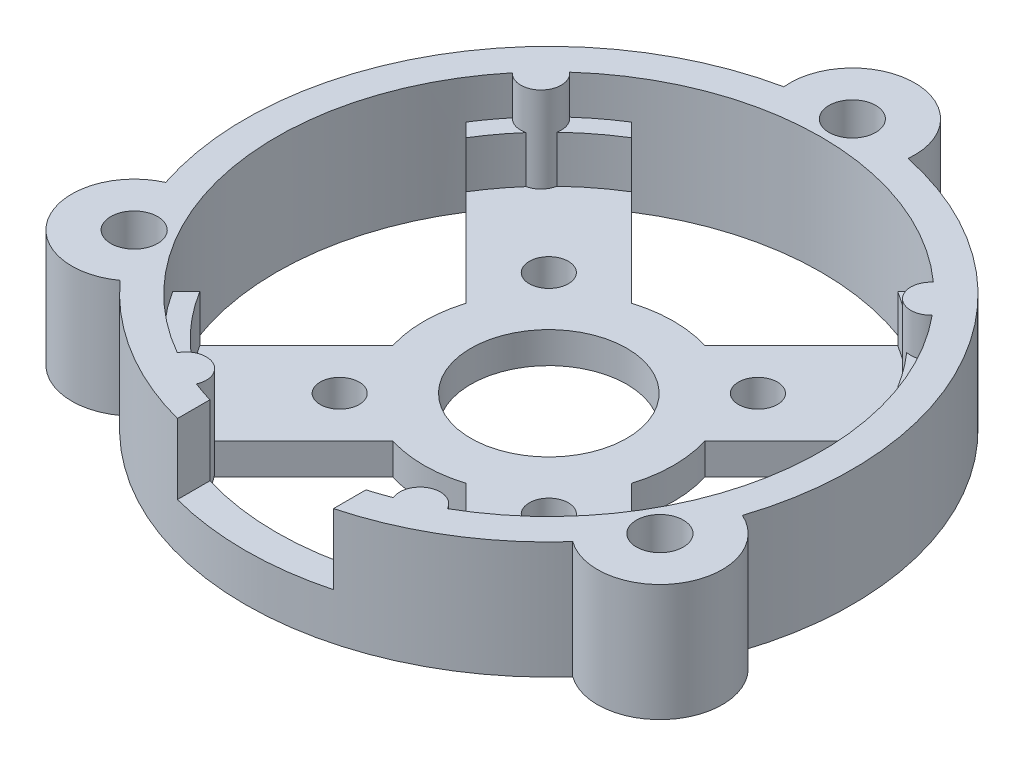
SolidWorks part; units mm, degrees
material "PLA"
ref_plane "Front" through (0, 0, 0) normal (0, 0, 1) x (1, 0, 0)
ref_plane "Top" through (0, 0, 0) normal (0, 1, 0) x (1, 0, 0)
ref_plane "Right" through (0, 0, 0) normal (1, 0, 0) x (0, 0, -1)
other "Configuration Table"
sketch "Esquisse1" plane through (0, 0, 0) normal (0, 1, 0) x (1, 0, 0)
  circle A0 centre (0, 0) radius 17.25 construction
  circle A1 centre (0, 0) radius 17.45
  circle A2 centre (0, 0) radius 19.45
  dimension "D1" = 34.5
  dimension "D2" = 0.2
  dimension "D3" = 2
extrude "Boss.-Extru.1" add sketch "Esquisse1" against normal blind 7.5
sketch "Esquisse2" plane through (0, -7.5, 0) normal (0, -1, 0) x (-1, 0, 0)
  line L0 (-10.8435, -16.1468) -> (16.1468, 10.8435)
  line L1 (-10.8435, -16.1468) -> (-16.1468, -10.8435) construction
  line L2 (16.1468, 10.8435) -> (10.8435, 16.1468) construction
  line L3 (-16.1468, -10.8435) -> (10.8435, 16.1468)
  line L4 (-10.8435, -16.1468) -> (10.8435, 16.1468) construction
  line L5 (16.1468, 10.8435) -> (-16.1468, -10.8435) construction
  line L6 (0, 0) -> (0, 19.45) construction
  line L7 (10.8435, -16.1468) -> (-16.1468, 10.8435)
  line L8 (10.8435, -16.1468) -> (16.1468, -10.8435) construction
  line L9 (-16.1468, 10.8435) -> (-10.8435, 16.1468) construction
  line L10 (16.1468, -10.8435) -> (-10.8435, 16.1468)
  line L11 (10.8435, -16.1468) -> (-10.8435, 16.1468) construction
  line L12 (-16.1468, 10.8435) -> (16.1468, -10.8435) construction
  line L14 (6.7, -6.7) -> (-6.7, -6.7) construction
  line L15 (6.7, -6.7) -> (6.7, 6.7) construction
  line L16 (6.7, 6.7) -> (-6.7, 6.7) construction
  line L17 (-6.7, -6.7) -> (-6.7, 6.7) construction
  line L18 (6.7, -6.7) -> (-6.7, 6.7) construction
  line L19 (6.7, 6.7) -> (-6.7, -6.7) construction
  circle A0 centre (0, 0) radius 17.45 construction
  circle A1 centre (0, 0) radius 19.45
  circle A2 centre (0, 0) radius 19.45
  circle A3 centre (0, 0) radius 17.45
  circle A4 centre (0, 0) radius 5
  circle A5 centre (0, 0) radius 8
  circle A6 centre (-6.7, 6.7) radius 1.25
  circle A7 centre (6.7, 6.7) radius 1.25
  circle A8 centre (6.7, -6.7) radius 1.25
  circle A9 centre (-6.7, -6.7) radius 1.25
  point P1 (0, 0)
  circle M30 centre (0, 0) radius 17.45
  dimension "D5" = 10
  dimension "D6" = 16
  dimension "D8" = 2.5
  dimension "D1" = 0
  dimension "D2" = 45
  dimension "D3" = 7.5
  dimension "D4" = 45
  dimension "D7" = 13.4
extrude "Boss.-Extru.2" add sketch "Esquisse2" against normal blind 2 contours A5 L7 L10 A8 M30 | L10 A5 L0 | L7 A5 L10 L0 A4 | L0 A5 L3 L10 A4 | A4 L0 L10 | A5 L0 L3 A7 M30 | A4 L10 L3 | L10 A5 L7 L3 A4 | A4 L3 L7 | L3 A5 L0 L7 A4 | L7 A5 L3 | A4 L7 L0 | L0 A5 L7 | L3 A5 L10 | A5 L10 L7 A6 M30 | A5 L3 L0 A9 M30 region at (8.9969, -7.5, 8.9969) region at (4.3011, -7.5, 4.3011) region at (0, -7.5, 7.021) region at (-8.9969, -7.5, 8.9969) region at (0, -7.5, 5.0989) region at (-4.3011, -7.5, 4.3011) region at (7.021, -7.5, 0) region at (8.9969, -7.5, -8.9969) region at (4.3011, -7.5, -4.3011) region at (5.0989, -7.5, 0) region at (-7.021, -7.5, 0) region at (-5.0989, -7.5, 0) region at (0, -7.5, -7.021) region at (-4.3011, -7.5, -4.3011) region at (-8.9969, -7.5, -8.9969) region at (0, -7.5, -5.0989)
sketch "Esquisse3" plane through (0, -5.5, 0) normal (0, 1, 0) x (1, 0, 0)
  line L0 (-2.3452, 7.6485) -> (-9.3991, 14.7024) construction
  line L1 (-2.3452, 7.6485) -> (-9.3991, 14.7024)
  line L10 (-7.6485, -2.3452) -> (-14.7024, -9.3991)
  line L11 (-9.3991, -14.7024) -> (-2.3452, -7.6485)
  line L12 (2.3452, -7.6485) -> (9.3991, -14.7024)
  line L13 (14.7024, -9.3991) -> (7.6485, -2.3452)
  line L14 (7.6485, 2.3452) -> (14.7024, 9.3991)
  line L15 (9.3991, 14.7024) -> (2.3452, 7.6485)
  line L16 (-2.3452, 7.6485) -> (-9.3991, 14.7024)
  line L17 (-14.7024, 9.3991) -> (-7.6485, 2.3452)
  line L18 (-7.6485, -2.3452) -> (-14.7024, -9.3991)
  line L19 (-9.3991, -14.7024) -> (-2.3452, -7.6485)
  line L20 (2.3452, -7.6485) -> (9.3991, -14.7024)
  line L21 (14.7024, -9.3991) -> (7.6485, -2.3452)
  line L22 (7.6485, 2.3452) -> (14.7024, 9.3991)
  line L23 (9.3991, 14.7024) -> (2.3452, 7.6485)
  line L24 (-2.3452, 7.6485) -> (-9.3991, 14.7024)
  line L25 (-14.7024, 9.3991) -> (-7.6485, 2.3452)
  arc A0 (-9.3991, 14.7024) -> (-14.7024, 9.3991) centre (0, 0) ccw construction
  arc A1 (-9.3991, 14.7024) -> (-14.7024, 9.3991) centre (0, 0) ccw
  arc A2 (14.7024, 9.3991) -> (9.3991, 14.7024) centre (0, 0) ccw construction
  arc A3 (14.7024, 9.3991) -> (9.3991, 14.7024) centre (0, 0) ccw
  arc A4 (-14.7024, -9.3991) -> (-9.3991, -14.7024) centre (0, 0) ccw construction
  arc A5 (-14.7024, -9.3991) -> (-9.3991, -14.7024) centre (0, 0) ccw
  arc A6 (9.3991, -14.7024) -> (14.7024, -9.3991) centre (0, 0) ccw construction
  arc A7 (9.3991, -14.7024) -> (14.7024, -9.3991) centre (0, 0) ccw
  circle A8 centre (0, 0) radius 16.25
  arc A17 (-7.6485, 2.3452) -> (-7.6485, -2.3452) centre (0, 0) ccw
  arc A18 (-14.7024, -9.3991) -> (-9.3991, -14.7024) centre (0, 0) ccw
  arc A19 (-2.3452, -7.6485) -> (2.3452, -7.6485) centre (0, 0) ccw
  arc A20 (9.3991, -14.7024) -> (14.7024, -9.3991) centre (0, 0) ccw
  arc A21 (7.6485, -2.3452) -> (7.6485, 2.3452) centre (0, 0) ccw
  arc A22 (14.7024, 9.3991) -> (9.3991, 14.7024) centre (0, 0) ccw
  arc A23 (-7.6485, 2.3452) -> (-7.6485, -2.3452) centre (0, 0) ccw
  arc A24 (-9.3991, 14.7024) -> (-14.7024, 9.3991) centre (0, 0) ccw
  arc A26 (-14.7024, -9.3991) -> (-9.3991, -14.7024) centre (0, 0) ccw
  arc A27 (-2.3452, -7.6485) -> (2.3452, -7.6485) centre (0, 0) ccw
  arc A28 (9.3991, -14.7024) -> (14.7024, -9.3991) centre (0, 0) ccw
  arc A29 (7.6485, -2.3452) -> (7.6485, 2.3452) centre (0, 0) ccw
  arc A30 (14.7024, 9.3991) -> (9.3991, 14.7024) centre (0, 0) ccw
  arc A32 (-9.3991, 14.7024) -> (-14.7024, 9.3991) centre (0, 0) ccw
  arc A33 (2.3452, 7.6485) -> (-2.3452, 7.6485) centre (0, 0) ccw
  arc A34 (2.3452, 7.6485) -> (-2.3452, 7.6485) centre (0, 0) ccw
  arc M20 (-14.7024, -9.3991) -> (-9.3991, -14.7024) centre (0, 0) ccw
  line M21 (-9.3991, -14.7024) -> (-2.3452, -7.6485)
  arc M24 (9.3991, -14.7024) -> (14.7024, -9.3991) centre (0, 0) ccw
  line M25 (14.7024, -9.3991) -> (7.6485, -2.3452)
  arc M28 (14.7024, 9.3991) -> (9.3991, 14.7024) centre (0, 0) ccw
  line M29 (9.3991, 14.7024) -> (2.3452, 7.6485)
  arc M32 (-9.3991, 14.7024) -> (-14.7024, 9.3991) centre (0, 0) ccw
  line M33 (-14.7024, 9.3991) -> (-7.6485, 2.3452)
  dimension "D1" = 32.5
  dimension "D2" = 0
extrude "Boss.-Extru.3" add sketch "Esquisse3" along normal blind 3 contours A8 L24 M32 M33 | A8 L22 M28 M29 | A8 L18 M20 M21 | A8 L20 M24 M25 region at (-11.8148, -5.5, -11.8148) region at (11.8148, -5.5, -11.8148) region at (-11.8148, -5.5, 11.8148) region at (11.8148, -5.5, 11.8148)
sketch "Esquisse4" plane through (0, -5.5, 0) normal (0, 1, 0) x (1, 0, 0)
  arc A0 (11.3631, 12.9785) -> (-11.3631, 12.9785) centre (0, 0) ccw
  arc A1 (11.3631, 12.9785) -> (13.4313, 10.8241) centre (12.5, 12) ccw
  arc A2 (8.7232, -14.8818) -> (6.055, -16.1524) centre (7.5, -15.75) ccw
  arc A3 (-13.4313, 10.8241) -> (-8.7232, -14.8818) centre (0, 0) ccw
  arc A4 (-6.055, -16.1524) -> (6.055, -16.1524) centre (0, 0) ccw
  arc A5 (8.7232, -14.8818) -> (13.4313, 10.8241) centre (0, 0) ccw
  arc A6 (-8.7232, -14.8818) -> (-6.055, -16.1524) centre (-7.5, -15.75) cw
  arc A7 (-11.3631, 12.9785) -> (-13.4313, 10.8241) centre (-12.5, 12) cw
  circle A8 centre (0, 0) radius 17.45 construction
  arc A9 (11.6545, 12.9875) -> (-11.6545, 12.9875) centre (0, 0) ccw
  arc A10 (-11.6545, 12.9875) -> (-13.4522, 11.1149) centre (-12.5, 12) cw
  arc A11 (-13.4522, 11.1149) -> (-8.6546, -15.1526) centre (0, 0) ccw
  arc A12 (-8.6546, -15.1526) -> (-6.3084, -16.2698) centre (-7.5, -15.75) cw
  arc A13 (-6.3084, -16.2698) -> (6.3084, -16.2698) centre (0, 0) ccw
  arc A14 (8.6546, -15.1526) -> (6.3084, -16.2698) centre (7.5, -15.75) ccw
  arc A15 (8.6546, -15.1526) -> (13.4522, 11.1149) centre (0, 0) ccw
  arc A16 (11.6545, 12.9875) -> (13.4522, 11.1149) centre (12.5, 12) ccw
  circle A17 centre (0, 0) radius 17.45
  arc M22 (13.832, 8.5287) -> (8.5287, 13.832) centre (0, 0) ccw
  arc M26 (-8.5287, 13.832) -> (-13.832, 8.5287) centre (0, 0) ccw
  dimension "D1" = 34.5
  dimension "D4" = 3
  dimension "D2" = 12
  dimension "D3" = 12.5
  dimension "D5" = 7.5
  dimension "D6" = 15.75
  dimension "D7" = 0.2
extrude "Boss.-Extru.4" add sketch "Esquisse4" along normal up to surface (5.5 mm away) contours A10 A17 M26 | A10 M26 | A16 M22 | A16 A17 M22 | A14 A17 | A12 A17 region at (11.6557, -5.5, -11.1895) region at (12.1811, -5.5, -11.6939) region at (-12.1811, -5.5, -11.6939) region at (-11.6557, -5.5, -11.1895) region at (-7.2603, -5.5, 15.2467) region at (7.2603, -5.5, 15.2467) up to face at (0, 0, 17.45)
chamfer "Chanfrein1" distance 1.5 angle 40 2 edges at (-7.5023, -5.5, 15.7549) (7.5023, -5.5, 15.7549) first distance on face at (-7.2217, -5.5, 15.1656) first distance on face at (7.2217, -5.5, 15.1656)
sketch "Esquisse5" plane through (0, 0, 0) normal (0, 1, 0) x (1, 0, 0)
  line L0 (0, 0) -> (0, 19.45) construction
  circle A0 centre (0, 19.45) radius 1.5
  circle A1 centre (0, 0) radius 19.45 construction
  circle A2 centre (0, 19.45) radius 4
  circle A3 centre (0, 0) radius 19.45
  circle M12 centre (0, 0) radius 19.45
  dimension "D1" = 3
  dimension "D2" = 8
extrude "Enlèv. mat.-Extru.1" cut sketch "Esquisse5" against normal up to surface (7.5 mm away) contours L0 A0 M12 | A0 L0 A3 region at (-0.6285, 0, -18.8031) region at (0.6285, 0, -18.8031) up to face at (-11.9502, -7.5, 0)
extrude "Boss.-Extru.5" add sketch "Esquisse5<3>" against normal up to surface (7.5 mm away) contours A2 A0 M12 region at (0, 0, -21.2294) up to face at (-11.9502, -7.5, 0)
sketch "Esquisse5<3>" plane through (0, 0, 0) normal (0, 1, 0) x (1, 0, 0) same geometry as "Esquisse5"
pattern_circular "Répétition circulaire1" count 2 every 120 about axis through (0, -7.5, 0) along (0, 1, 0) of "Enlèv. mat.-Extru.1", "Boss.-Extru.5" other way count 2
sketch "Esquisse6" plane through (0, 0, 0) normal (0, 1, 0) x (1, 0, 0)
  line L1 (-5, -14.95) -> (5, -14.95)
  line L2 (-5, -14.95) -> (-5, -19.95)
  line L3 (-5, -19.95) -> (5, -19.95)
  line L4 (5, -14.95) -> (5, -19.95)
  line L5 (-5, -14.95) -> (5, -19.95) construction
  line L6 (-5, -19.95) -> (5, -14.95) construction
  arc A0 (-6.3084, -16.2698) -> (6.3084, -16.2698) centre (0, 0) ccw construction
  point P0 (0, -17.45)
  dimension "D1" = 10
  dimension "D2" = 5
extrude "Enlèv. mat.-Extru.2" cut sketch "Esquisse6" against normal offset from surface (4.5 mm away) 3 up to face at (0, -7.5, 0)
